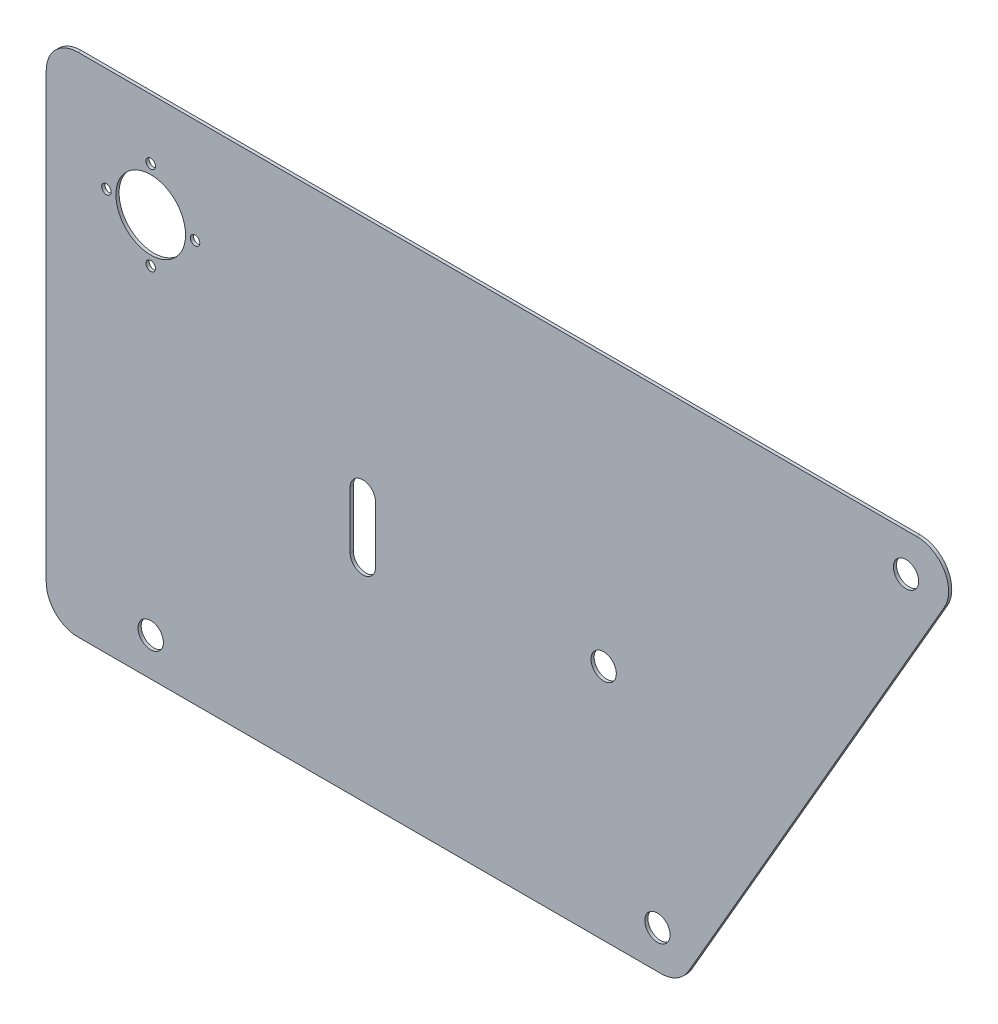
SolidWorks part; units mm, degrees
ref_plane "Front Plane" through (0, 0, 0) normal (0, 0, 1) x (1, 0, 0)
ref_plane "Top Plane" through (0, 0, 0) normal (0, 1, 0) x (1, 0, 0)
ref_plane "Right Plane" through (0, 0, 0) normal (1, 0, 0) x (0, 0, -1)
sketch "Sketch1" plane through (0, 0, 0) normal (0, 0, 1) x (1, 0, 0)
  line L0 (100, 80) -> (192.376, 80)
  line L1 (-100, -80) -> (100, -80)
  line L2 (-100, -80) -> (-100, 80)
  line L3 (-100, 80) -> (100, 80)
  line L4 (100, -80) -> (100, 80)
  line L5 (-100, -80) -> (100, 80) construction
  line L6 (-100, 80) -> (100, -80) construction
  line L7 (192.376, 80) -> (100, -80)
  line L8 (100, 80) -> (100, -80)
  point P0 (0, 0)
  dimension "D1" = 160
  dimension "D2" = 200
  dimension "D3" = 30
extrude "Boss-Extrude1" add sketch "Sketch1" along normal blind 1 contours L1 L4 L3 L2 | L7 L0 L4 region at (0, 0, 0) region at (130.792, 26.6667, 0)
fillet "Fillet1" radius 10 4 edges at (192.376, 80, 0.5) (100, -80, 0.5) (-100, -80, 0.5) (-100, 80, 0.5)
sketch "Sketch2" plane through (0, 0, 1) normal (0, 0, 1) x (1, 0, 0)
  line L0 (-90, -80) -> (94.2265, -80) construction
  line L1 (183.7158, 65) -> (102.8868, -75) construction
  line L2 (-90, 80) -> (175.0555, 80) construction
  line L3 (-100, -70) -> (-100, 70) construction
  line L4 (0, -14) -> (0, 4) construction
  line L5 (-4, -14) -> (-4, 4)
  line L6 (4, -14) -> (4, 4)
  line L8 (0, -0.55) -> (0, 0.55) construction
  circle A0 centre (93.0718, -68) radius 4
  circle A1 centre (171.5914, 68) radius 4
  circle A2 centre (-67, 47) radius 11
  circle A3 centre (-67, -68) radius 4
  circle A4 centre (-53, 47) radius 1.5
  circle A5 centre (-67, 61) radius 1.5
  circle A6 centre (-81, 47) radius 1.5
  circle A7 centre (-67, 33) radius 1.5
  arc A8 (-4, -14) -> (4, -14) centre (0, -14) ccw
  arc A9 (4, 4) -> (-4, 4) centre (0, 4) ccw
  circle A10 centre (76.0815, -5) radius 4
  point P24 (0, -5)
  dimension "D3" = 8
  dimension "D4" = 8
  dimension "D9" = 22
  dimension "D10" = 8
  dimension "D12" = 3
  dimension "D13" = 3
  dimension "D14" = 3
  dimension "D15" = 3
  dimension "D16" = 14
  dimension "D20" = 4
  dimension "D22" = 8
  dimension "D1" = 12
  dimension "D2" = 12
  dimension "D5" = 12
  dimension "D6" = 12
  dimension "D7" = 33
  dimension "D8" = 33
  dimension "D11" = 12
  dimension "D17" = 14
  dimension "D18" = 14
  dimension "D19" = 14
  dimension "D21" = 18
  dimension "D23" = 85
  dimension "D24" = 85
extrude "Cut-Extrude1" cut sketch "Sketch2" against normal blind 3
